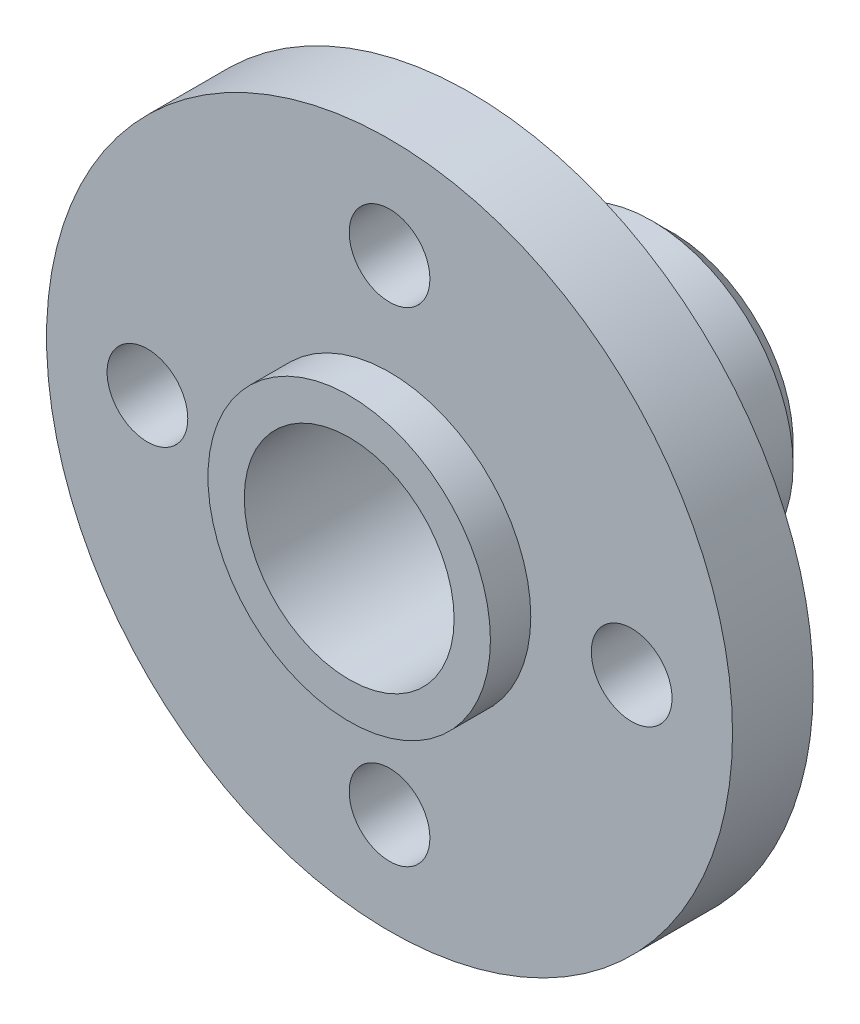
SolidWorks part; units mm, degrees
material "ABS"
ref_plane "Спереди" through (0, 0, 0) normal (0, 0, 1) x (1, 0, 0)
ref_plane "Сверху" through (0, 0, 0) normal (0, 1, 0) x (1, 0, 0)
ref_plane "Справа" through (0, 0, 0) normal (1, 0, 0) x (0, 0, -1)
sketch "Эскиз2" plane through (0, 0, 0) normal (0, 0, 1) x (1, 0, 0)
  line L0 (0, 0) -> (-8.5, 0) construction
  circle A0 centre (0, 0) radius 2.6
  circle A1 centre (0, 0) radius 8.5
  circle A2 centre (-6, 0) radius 1
  circle A3 centre (0, 6) radius 1
  circle A4 centre (6, 0) radius 1
  circle A5 centre (0, -6) radius 1
  point P16 (0, 0)
  dimension "D1" = 17
  dimension "D2" = 5.2
  dimension "D3" = 2
  dimension "D4" = 6
  dimension "D5" = 4
extrude "Бобышка-Вытянуть1" add sketch "Эскиз2" along normal blind 2
sketch "Эскиз3" plane through (0, 0, 2) normal (0, 0, 1) x (1, 0, 0)
  circle A0 centre (0, 0) radius 2.6
  circle A1 centre (0, 0) radius 3.5
  dimension "D1" = 7
  dimension "D2" = 5.2
extrude "Бобышка-Вытянуть2" add sketch "Эскиз3" along normal blind 1
sketch "Эскиз4" plane through (0, 0, 0) normal (0, 0, -1) x (-1, 0, 0)
  circle A0 centre (0, 0) radius 3.5
  circle A1 centre (0, 0) radius 2.6
  dimension "D1" = 7
extrude "Бобышка-Вытянуть3" add sketch "Эскиз4" along normal blind 5
chamfer "Фаска1" distance 0.5 angle 45 1 edges at (-3.5, 0, -5)
